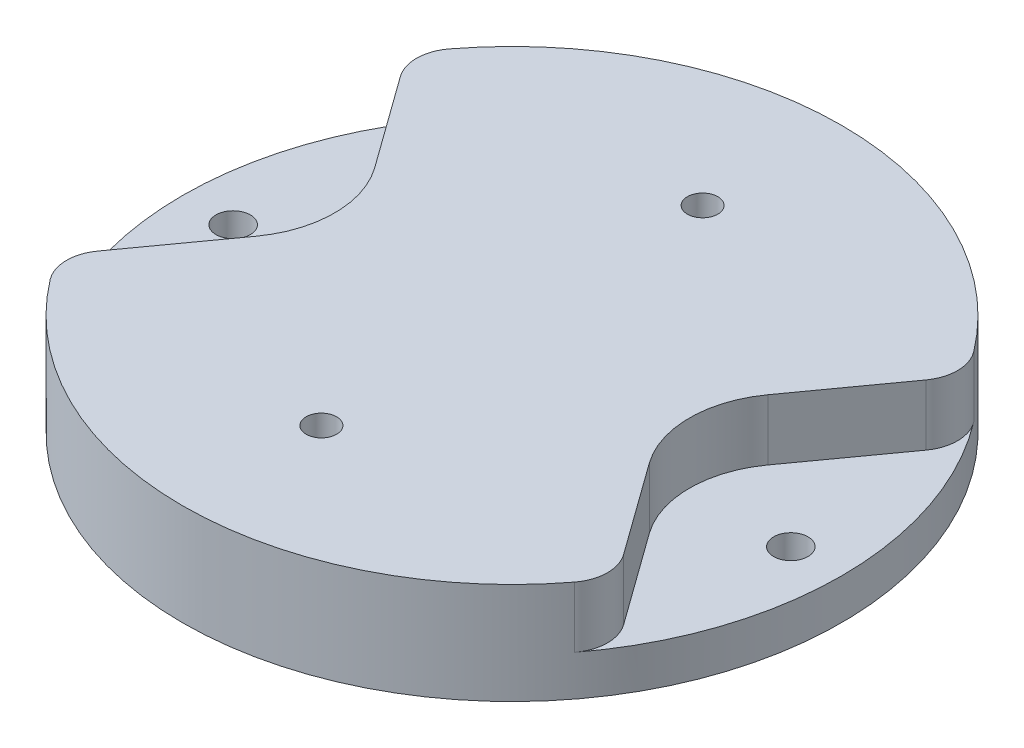
SolidWorks part; units mm, degrees
ref_plane "Front Plane" through (0, 0, 0) normal (0, 0, 1) x (1, 0, 0)
ref_plane "Top Plane" through (0, 0, 0) normal (0, 1, 0) x (1, 0, 0)
ref_plane "Right Plane" through (0, 0, 0) normal (1, 0, 0) x (0, 0, -1)
sketch "Sketch1" plane through (0, 0, 0) normal (0, 1, 0) x (1, 0, 0)
  line L0 (-34.925, 0) -> (34.925, 0) construction
  line L1 (0, 23.876) -> (0, -23.876) construction
  line L2 (-24.6219, 7.4253) -> (-35.0174, 21.8497)
  line L3 (-24.6219, -7.4253) -> (-35.0174, -21.8497)
  line L4 (24.6219, 7.4253) -> (35.0174, 21.8497)
  line L5 (24.6219, -7.4253) -> (35.0174, -21.8497)
  circle A0 centre (0, 0) radius 41.275
  circle A1 centre (-34.925, 0) radius 2.15
  circle A2 centre (34.925, 0) radius 2.15
  circle A3 centre (0, 23.876) radius 1.905
  circle A4 centre (0, -23.876) radius 1.905
  circle A5 centre (0, 23.876) radius 7.62
  circle A6 centre (0, -23.876) radius 7.62
  circle A7 centre (-34.925, 0) radius 12.7
  circle A8 centre (34.925, 0) radius 12.7
  dimension "D1" = 82.55
  dimension "D2" = 4.3
  dimension "D4" = 47.752
  dimension "D5" = 3.81
  dimension "D6" = 25.4
  dimension "D7" = 15.24
  dimension "D3" = 69.85
  dimension "D8" = 17.78
extrude "Boss-Extrude1" add sketch "Sketch1" along normal blind 12.7 contours A0
extrude "Cut-Extrude2" cut sketch "Sketch1<4>" along normal through all contours A3 | A2 | A4 | A1
sketch "Sketch1<4>" plane through (0, 0, 0) normal (0, 1, 0) x (1, 0, 0) same geometry as "Sketch1"
extrude "Cut-Extrude3" cut sketch "Sketch1<5>" along normal blind 5.08 contours A6 A4 | A5 A3 | A5 | A6 region at (-7.4045, 0, -23.876) region at (-7.4045, 0, 23.876)
sketch "Sketch1<5>" plane through (0, 0, 0) normal (0, 1, 0) x (1, 0, 0) same geometry as "Sketch1"
extrude "Cut-Extrude4" cut sketch "Sketch1<6>" against normal blind 7.62 from surface contours A7 A0 L3 | A7 L2 A0 | A8 A0 L4 | A8 L5 A0 | A7 | A8 region at (-33.8712, 0, -15.2998) region at (33.8712, 0, -15.2998) region at (-33.8712, 0, 15.2998) region at (33.8712, 0, 15.2998) starting at face at (0, 12.7, -21.971)
sketch "Sketch1<6>" plane through (0, 0, 0) normal (0, 1, 0) x (1, 0, 0) same geometry as "Sketch1"
fillet "Fillet1" radius 5.08 4 edges at (35.0174, 8.89, 21.8497) (35.0174, 8.89, -21.8497) (-35.0174, 8.89, 21.8497) (-35.0174, 8.89, -21.8497)
